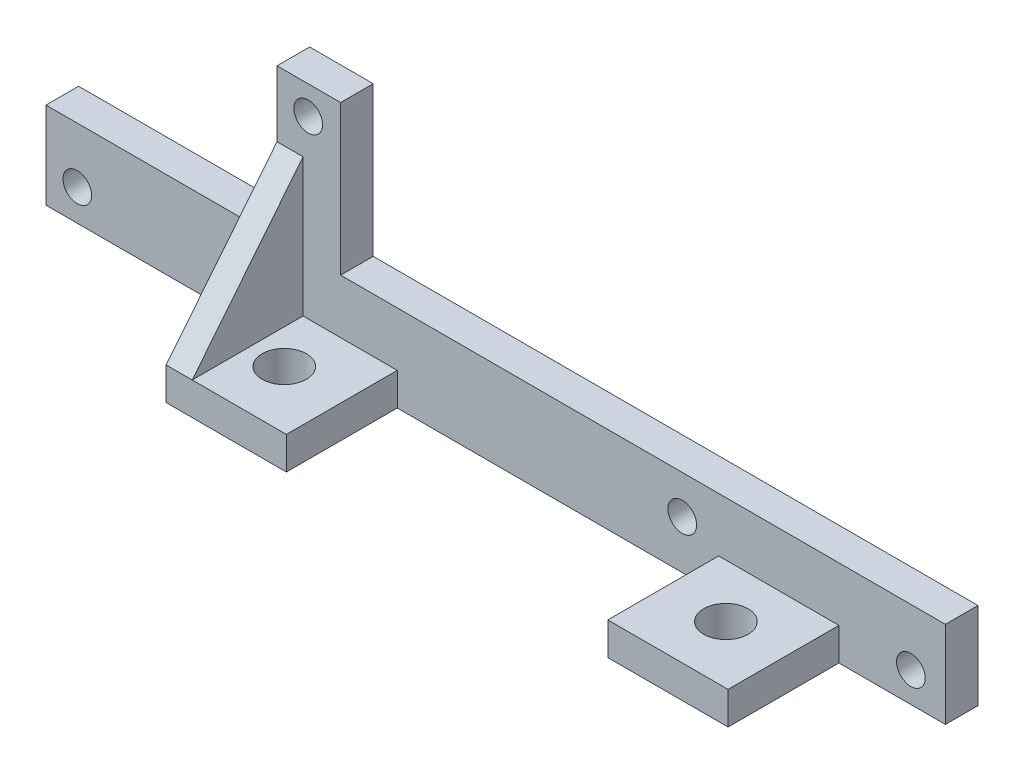
SolidWorks part; units mm, degrees
ref_plane "Front Plane" through (0, 0, 0) normal (0, 0, 1) x (1, 0, 0)
ref_plane "Top Plane" through (0, 0, 0) normal (0, 1, 0) x (1, 0, 0)
ref_plane "Right Plane" through (0, 0, 0) normal (1, 0, 0) x (0, 0, -1)
sketch "Sketch1" plane through (0, 0, 0) normal (0, 0, 1) x (1, 0, 0)
  line L1 (-43, 11.5) -> (43, 11.5)
  line L2 (-43, 11.5) -> (-43, -11.5)
  line L3 (-43, -11.5) -> (43, -11.5)
  line L4 (43, 11.5) -> (43, -11.5)
  point P0 (0, 0)
  dimension "D1" = 86
  dimension "D2" = 23
extrude "Boss-Extrude1" add sketch "Sketch1" against normal blind 3.175 contours L2 L1 L4 L3
ref_plane "Plane1" through (0, -11.5, 0) normal (0, -1, 0) x (-1, 0, 0)
sketch "Sketch3" plane through (0, -11.5, 0) normal (0, -1, 0) x (-1, 0, 0)
  line L0 (34.2, 0) -> (34.2, -10.795)
  line L1 (34.2, -10.795) -> (8.8, -10.795)
  line L2 (8.8, -10.795) -> (8.8, 0)
  line L3 (43, 0) -> (-43, 0) construction
  line L4 (34.2, 0) -> (8.8, 0)
  line L5 (0, 19.3889) -> (0, -14.044) construction
  line L6 (-34.2, 0) -> (-34.2, -10.795)
  line L7 (-34.2, -10.795) -> (-8.8, -10.795)
  line L8 (-8.8, -10.795) -> (-8.8, 0)
  line L9 (-34.2, 0) -> (-8.8, 0)
  line L10 (43, 3.175) -> (-43, 3.175) construction
  point P13 (21.5, 0)
  dimension "D2" = 13.97
  dimension "D3" = 21.5
extrude "Boss-Extrude2" add sketch "Sketch3" against normal blind 3.175
sketch "Sketch13" plane through (0, 11.5, 0) normal (0, 1, 0) x (1, 0, 0)
  line L0 (0, 3.175) -> (0, 0)
  line L1 (-43, 3.175) -> (43, 3.175) construction
ref_plane "Plane4" through (0, 0, 0) normal (1, 0, 0) x (0, 0, -1)
ref_plane "Plane6" through (0, 11.5, 0) normal (0, 1, 0) x (1, 0, 0)
sketch "Sketch18" plane through (0, 11.5, 0) normal (0, 1, 0) x (1, 0, 0)
  line L0 (-21.5, -10.795) -> (-21.5, 10.3861) construction
  line L1 (-8.8, -10.795) -> (-34.2, -10.795) construction
  line L2 (0, 8.5709) -> (0, -12.3789) construction
  circle A2 centre (-14.6263, -5.1774) radius 2.159
  circle A3 centre (28.3737, -5.1774) radius 2.159
extrude "Cut-Extrude2" cut sketch "Sketch18" against normal blind 127
sketch "Sketch19" plane through (0, 0, -3.175) normal (0, 0, -1) x (-1, 0, 0)
  circle A5 centre (-41.206, -8.579) radius 1.397
  circle A6 centre (-18.9429, -6.801) radius 1.397
  circle A7 centre (17.473, 8.7438) radius 1.397
  circle A8 centre (39.952, -8.452) radius 1.397
extrude "Cut-Extrude3" cut sketch "Sketch19" against normal through all
sketch "Sketch27" plane through (0, 0, -3.175) normal (0, 0, -1) x (-1, 0, 0)
  line L1 (-43, 11.5) -> (14.3155, 11.5)
  line L2 (-43, 11.5) -> (-43, -3.0562)
  line L3 (-43, -3.0562) -> (14.3155, -3.0562)
  line L4 (14.3155, 11.5) -> (14.3155, -3.0562)
  line L5 (43, 11.5) -> (20.5101, 11.5)
  line L6 (43, 11.5) -> (43, -3.0562)
  line L7 (43, -3.0562) -> (20.5101, -3.0562)
  line L8 (20.5101, 11.5) -> (20.5101, -3.0562)
  circle A0 centre (-18.9429, -6.801) radius 1.397 construction
  point P10 (20.5101, -3.0562)
  point P14 (-18.9429, -5.404)
  dimension "D1" = 2.3478
sketch "Sketch28" plane through (0, 0, -3.175) normal (0, 0, -1) x (-1, 0, 0)
  line L4 (-43, -11.5) -> (-43, -3.0562)
  line L5 (-43, -11.5) -> (-44.5635, -11.5)
  line L6 (-43, -3.0562) -> (-44.5635, -3.0562)
  line L7 (-44.5635, -11.5) -> (-44.5635, -3.0562)
  line L8 (-43, 11.5) -> (-43, -11.5) construction
  point P9 (-44.5635, -11.5)
  dimension "D1" = 8.4438
extrude "Boss-Extrude4" add sketch "Sketch28" against normal blind 3.175
extrude "Cut-Extrude5" cut sketch "Sketch27" against normal blind 3.175
sketch "Sketch29" plane through (0, 11.5, 0) normal (0, 1, 0) x (1, 0, 0)
  line L6 (8.8, 0) -> (22.4899, 0)
  line L7 (8.8, 0) -> (8.8, -10.795)
  line L8 (8.8, -10.795) -> (22.4899, -10.795)
  line L9 (22.4899, 0) -> (22.4899, -10.795)
  line L15 (-8.8, -10.795) -> (-34.2, -10.795) construction
  line L16 (-34.2, 0) -> (-20.5101, 0)
  line L17 (-34.2, 0) -> (-34.2, -10.795)
  line L18 (-34.2, -10.795) -> (-20.5101, -10.795)
  line L19 (-20.5101, 0) -> (-20.5101, -10.795)
  point P15 (0, 0)
  dimension "D1" = 13.6899
  dimension "D2" = 13.6899
extrude "Cut-Extrude6" cut sketch "Sketch29" against normal blind 50.8
ref_plane "Plane7" through (-20.5101, 0, 0) normal (-1, 0, 0) x (0, 0, 1)
sketch "Sketch30" plane through (-20.5101, 0, 0) normal (-1, 0, 0) x (0, 0, 1)
  line L0 (0, 5.0998) -> (10.795, -8.325)
  line L1 (0, 11.5) -> (0, -3.0562) construction
  point P5 (0, 0)
rib "Rib3" sketch "Sketch30" sketch "Sketch30" thickness 2.54 extrusion direction parallel to sketch draft on no parameters "D1"=2.54
